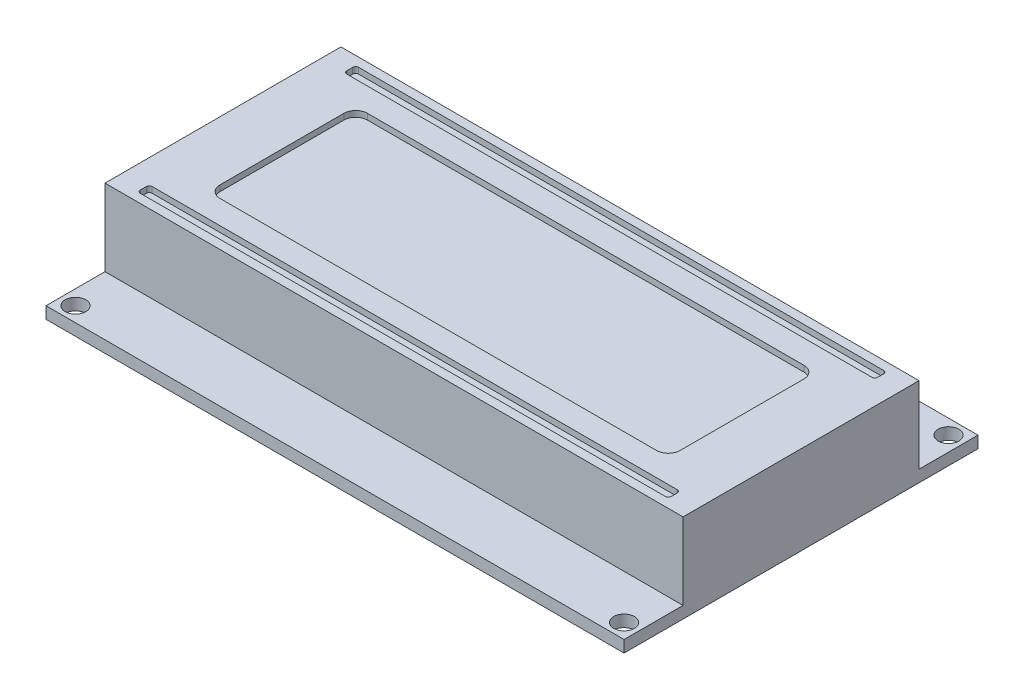
SolidWorks part; units mm, degrees
ref_plane "Front Plane" through (0, 0, 0) normal (0, 0, 1) x (1, 0, 0)
ref_plane "Top Plane" through (0, 0, 0) normal (0, 1, 0) x (1, 0, 0)
ref_plane "Right Plane" through (0, 0, 0) normal (1, 0, 0) x (0, 0, -1)
sketch "Sketch1" plane through (0, 0, 0) normal (0, 1, 0) x (1, 0, 0)
  line L0 (75, 55) -> (75, 0) construction
  line L1 (0, 0) -> (150, 0)
  line L2 (0, 0) -> (0, 55)
  line L3 (0, 55) -> (150, 55)
  line L4 (150, 0) -> (150, 55)
  line L5 (0, 27.5) -> (150, 27.5) construction
  circle A0 centre (3, 52) radius 1.5
  circle A1 centre (147, 52) radius 1.5
  circle A2 centre (147, 3) radius 1.5
  circle A3 centre (3, 3) radius 1.5
  dimension "D3" = 3
  dimension "D1" = 55
  dimension "D2" = 150
  dimension "D4" = 3
  dimension "D5" = 3
extrude "Boss-Extrude1" add sketch "Sketch1" along normal blind 2
sketch "Sketch2" plane through (0, 2, 0) normal (0, 1, 0) x (1, 0, 0)
  line L0 (0, 0) -> (150, 0) construction
  line L1 (0, 0) -> (0, 55) construction
  circle A0 centre (13, 10) radius 6
  dimension "D1" = 12
  dimension "D2" = 10
  dimension "D3" = 13
extrude "Boss-Extrude2" add sketch "Sketch2" along normal blind 10
sketch "Sketch3" plane through (0, 2, 0) normal (0, 1, 0) x (1, 0, 0)
  line L0 (0, 27.5) -> (150, 27.5) construction
  line L1 (7, 33.5) -> (19, 33.5)
  line L2 (7, 33.5) -> (7, 21.5)
  line L3 (7, 21.5) -> (19, 21.5)
  line L4 (19, 33.5) -> (19, 21.5)
  line L5 (13, 0) -> (13, 55) construction
  line L6 (0, 0) -> (150, 0) construction
  line L7 (0, 55) -> (150, 55) construction
  line L8 (7, 27.5) -> (19, 27.5) construction
  circle A1 centre (13, 10) radius 6 construction
  point P4 (7, 27.5)
  point P16 (13, 27.5)
  point P19 (13, 16)
  dimension "D1" = 12
  dimension "D2" = 12
extrude "Boss-Extrude3" add sketch "Sketch3" along normal blind 25
sketch "Sketch4" plane through (0, 2, 0) normal (0, 1, 0) x (1, 0, 0)
  line L0 (13, 45.5) -> (13, 40.5) construction
  line L1 (10.5, 45.5) -> (15.5, 45.5)
  line L2 (10.5, 45.5) -> (10.5, 40.5)
  line L3 (10.5, 40.5) -> (15.5, 40.5)
  line L4 (15.5, 45.5) -> (15.5, 40.5)
  line L5 (10.5, 43) -> (15.5, 43) construction
  line L7 (13, 0) -> (13, 55) construction
  line L8 (7, 33.5) -> (19, 33.5) construction
  line L9 (150, 0) -> (150, 55) construction
  line L10 (127, 8) -> (86, 8)
  line L11 (127, 8) -> (127, 5)
  line L12 (127, 5) -> (86, 5)
  line L13 (86, 8) -> (86, 5)
  line L14 (0, 0) -> (150, 0) construction
  point P8 (13, 43)
  dimension "D1" = 5
  dimension "D2" = 5
  dimension "D3" = 7
  dimension "D4" = 23
  dimension "D5" = 41
  dimension "D6" = 3
  dimension "D7" = 5
extrude "Boss-Extrude4" add sketch "Sketch4" along normal blind 5
sketch "Sketch5" plane through (0, 7, 0) normal (0, 1, 0) x (1, 0, 0)
  line L0 (86, 5) -> (127, 5) construction
  line L1 (86, 8) -> (127, 8)
  line L2 (86, 8) -> (86, 5)
  line L3 (86, 5) -> (127, 5)
  line L4 (127, 8) -> (127, 5)
  line L5 (86, 5) -> (127, 5) construction
  line L6 (10.5, 43) -> (15.5, 43) construction
  line L7 (10.5, 45.5) -> (10.5, 40.5) construction
  line L8 (15.5, 40.5) -> (15.5, 45.5) construction
  line L10 (10.5, 45.5) -> (15.5, 45.5)
  line L11 (10.5, 45.5) -> (10.5, 40.5)
  line L12 (10.5, 40.5) -> (15.5, 40.5)
  line L13 (15.5, 45.5) -> (15.5, 40.5)
  circle A0 centre (13, 43) radius 1.5
  point P15 (13, 43)
  dimension "D1" = 3
extrude "Cut-Extrude1" cut sketch "Sketch5" against normal blind 2
sketch "Sketch6" plane through (0, 27, 0) normal (0, 1, 0) x (1, 0, 0)
  line L0 (10.3706, 26.0556) -> (15.6294, 26.0556)
  line L1 (7, 33.5) -> (19, 33.5)
  line L2 (7, 33.5) -> (7, 21.5)
  line L3 (7, 21.5) -> (19, 21.5)
  line L4 (19, 33.5) -> (19, 21.5)
  arc A0 (15.6294, 26.0556) -> (10.3706, 26.0556) centre (13, 27.5) ccw
  dimension "D1" = 6
extrude "Cut-Extrude2" cut sketch "Sketch6" against normal blind 13
sketch "Sketch7" plane through (0, 14, 0) normal (0, 1, 0) x (1, 0, 0)
  line L1 (7, 33.5) -> (19, 33.5)
  line L2 (7, 33.5) -> (7, 21.5)
  line L3 (7, 21.5) -> (19, 21.5)
  line L4 (19, 33.5) -> (19, 21.5)
  circle A0 centre (13, 27.5) radius 3.5
  line M4 (7, 33.5) -> (7, 21.5)
  line M5 (7, 21.5) -> (19, 21.5)
  line M6 (19, 21.5) -> (19, 33.5)
  line M7 (19, 33.5) -> (7, 33.5)
  dimension "D1" = 7
extrude "Cut-Extrude3" cut sketch "Sketch7" against normal blind 7 contours A0 M7 M4 M5 M6 region at (13, 14, -33.3303)
sketch "Sketch8" plane through (0, 12, 0) normal (0, 1, 0) x (1, 0, 0)
  circle A0 centre (13, 10) radius 1.25
  point P0 (13, 10)
  dimension "D1" = 2.5
extrude "Cut-Extrude4" cut sketch "Sketch8" against normal blind 5
sketch "Sketch9" plane through (0, 0, 0) normal (0, -1, 0) x (1, 0, 0)
  line L0 (0, -55) -> (150, -55) construction
  line L1 (149, -20) -> (131, -20)
  line L2 (149, -20) -> (149, -47)
  line L3 (149, -47) -> (124, -47)
  line L4 (124, -22) -> (124, -47)
  line L5 (150, 0) -> (150, -55) construction
  line L6 (124, -22) -> (129, -22)
  line L7 (129, -22) -> (131, -20)
  dimension "D1" = 8
  dimension "D2" = 27
  dimension "D3" = 1
  dimension "D4" = 25
  dimension "D5" = 2
  dimension "D6" = 5
  dimension "D7" = 45
extrude "Boss-Extrude5" add sketch "Sketch9" along normal blind 3
sketch "Sketch10" plane through (149, 0, 0) normal (1, 0, 0) x (0, 0, -1)
  line L0 (20, -1.5) -> (47, -1.5) construction
  line L1 (20, -3) -> (20, 0) construction
  line L2 (47, -3) -> (47, 0) construction
  line L3 (33.5, -3) -> (33.5, 0) construction
  line L4 (47, -3) -> (20, -3) construction
  line L5 (0, 0) -> (55, 0) construction
  line L6 (33.5, -2.25) -> (33.5, -0.75) construction
  line L7 (21, -2.25) -> (46, -2.25)
  line L8 (21, -2.25) -> (21, -0.75)
  line L9 (21, -0.75) -> (46, -0.75)
  line L10 (46, -2.25) -> (46, -0.75)
  line L11 (21, -1.5) -> (46, -1.5) construction
  point P20 (33.5, -1.5)
  point P21 (33.5, -1.5)
  dimension "D1" = 1.5
  dimension "D2" = 25
extrude "Cut-Extrude5" cut sketch "Sketch10" against normal blind 18
sketch "Sketch11" plane through (0, 5, 0) normal (0, 1, 0) x (1, 0, 0)
  line L0 (0, 0) -> (150, 0) construction
  line L1 (136, 64) -> (38, 64)
  line L2 (136, 64) -> (136, 4)
  line L3 (136, 4) -> (38, 4)
  line L4 (38, 64) -> (38, 4)
  line L5 (150, 0) -> (150, 55) construction
  line L6 (87, 64) -> (87, 4) construction
  line L7 (38, 34) -> (136, 34) construction
  circle A0 centre (40.5, 61.5) radius 1.75
  circle A1 centre (133.5, 61.5) radius 1.75
  circle A2 centre (133.5, 6.5) radius 1.75
  circle A3 centre (40.5, 6.5) radius 1.75
  point P12 (87, 34)
  dimension "D5" = 3.5
  dimension "D1" = 98
  dimension "D2" = 60
  dimension "D3" = 4
  dimension "D4" = 14
  dimension "D6" = 2.5
  dimension "D7" = 2.5
extrude "Boss-Extrude6" add sketch "Sketch11" along normal blind 2
sketch "Sketch12" plane through (0, 7, 0) normal (0, 1, 0) x (1, 0, 0)
  line L0 (38, 34) -> (136, 34) construction
  line L1 (38, 54) -> (136, 54)
  line L2 (38, 54) -> (38, 14)
  line L3 (38, 14) -> (136, 14)
  line L4 (136, 54) -> (136, 14)
  dimension "D1" = 40
extrude "Boss-Extrude7" add sketch "Sketch12" along normal blind 13
sketch "Sketch13" plane through (0, 20, 0) normal (0, 1, 0) x (1, 0, 0)
  line L0 (87, 54) -> (87, 14) construction
  line L1 (136, 54) -> (38, 54) construction
  line L2 (38, 14) -> (136, 14) construction
  line L3 (38, 34) -> (136, 34) construction
  line L4 (38, 54) -> (38, 14) construction
  line L5 (136, 14) -> (136, 54) construction
  line L6 (87, 46.5) -> (87, 21.5) construction
  line L7 (50, 46.5) -> (124, 46.5)
  line L8 (48, 44.5) -> (48, 23.5)
  line L9 (50, 21.5) -> (124, 21.5)
  line L10 (126, 44.5) -> (126, 23.5)
  line L11 (87, 52.5) -> (87, 50.5) construction
  line L12 (42.5, 52.5) -> (131.5, 52.5)
  line L13 (42, 52) -> (42, 51)
  line L14 (42.5, 50.5) -> (131.5, 50.5)
  line L15 (132, 52) -> (132, 51)
  line L16 (136, 54) -> (38, 54) construction
  line L17 (42, 52.5) -> (42, 50.5)
  line L18 (132, 52.5) -> (132, 50.5)
  line L19 (87, 15.5) -> (87, 17.5) construction
  line L20 (132, 16) -> (132, 17)
  line L21 (42, 16) -> (42, 17)
  line L22 (132, 15.5) -> (132, 17.5)
  line L23 (42.5, 17.5) -> (131.5, 17.5)
  line L24 (42, 15.5) -> (42, 17.5)
  line L25 (42.5, 15.5) -> (131.5, 15.5)
  arc A0 (131.5, 50.5) -> (132, 51) centre (131.5, 51) ccw
  arc A1 (131.5, 52.5) -> (132, 52) centre (131.5, 52) cw
  arc A2 (42, 51) -> (42.5, 50.5) centre (42.5, 51) ccw
  arc A3 (42.5, 52.5) -> (42, 52) centre (42.5, 52) ccw
  arc A4 (131.5, 15.5) -> (132, 16) centre (131.5, 16) ccw
  arc A5 (131.5, 17.5) -> (132, 17) centre (131.5, 17) cw
  arc A6 (42.5, 15.5) -> (42, 16) centre (42.5, 16) cw
  arc A7 (42.5, 17.5) -> (42, 17) centre (42.5, 17) ccw
  arc A8 (124, 46.5) -> (126, 44.5) centre (124, 44.5) cw
  arc A9 (48, 23.5) -> (50, 21.5) centre (50, 23.5) ccw
  arc A10 (50, 46.5) -> (48, 44.5) centre (50, 44.5) ccw
  arc A11 (124, 21.5) -> (126, 23.5) centre (124, 23.5) ccw
  point P18 (87, 34)
  point P19 (87, 34)
  point P62 (48, 21.5)
  point P65 (48, 46.5)
  dimension "D6" = 0.5
  dimension "D7" = 0.5
  dimension "D8" = 2
  dimension "D1" = 25
  dimension "D2" = 10
  dimension "D3" = 4
  dimension "D4" = 1.5
  dimension "D5" = 2
extrude "Cut-Extrude6" cut sketch "Sketch13" against normal blind 1 contours L15 L12 L13 L14 | L10 L7 L8 L9 | L21 L25 L20 L23 region at (87, 20, -34) region at (87, 20, -51.5) region at (87, 20, -16.5)
sketch "Sketch14" plane through (131, 0, 0) normal (1, 0, 0) x (0, 0, -1)
  line L1 (21, -0.75) -> (46, -0.75)
  line L2 (21, -0.75) -> (21, -2.25)
  line L3 (21, -2.25) -> (46, -2.25)
  line L4 (46, -0.75) -> (46, -2.25)
extrude "Boss-Extrude8" add sketch "Sketch14" along normal offset from surface (29 mm away) 11 up to face at (149, -1.5, -33.5) offset beyond the face yes
sketch "Sketch15" plane through (0, 2, 0) normal (0, 1, 0) x (1, 0, 0)
  line L1 (38, 64) -> (-8.6907, 64)
  line L2 (38, 64) -> (38, 4)
  line L3 (38, -2.9807) -> (-8.6907, -2.9807)
  line L4 (-8.6907, 64) -> (-8.6907, -2.9807)
  line L5 (38, 4) -> (136, 4)
  line L7 (38, -2.9807) -> (158.5564, -2.9807)
  line L8 (158.5564, 4) -> (158.5564, -2.9807)
  line L9 (158.5564, 4) -> (165.161, 4)
  line L10 (136, 4) -> (136, 64)
  line L11 (136, 64) -> (165.161, 64)
  line L12 (165.161, 4) -> (165.161, 64)
extrude "Cut-Extrude7" cut sketch "Sketch15" against normal blind 10 and the other way blind 76
sketch "Sketch16" plane through (0, 0, -4) normal (0, 0, 1) x (1, 0, 0)
  line L1 (38, 5) -> (136, 5)
  line L2 (38, 5) -> (38, -3)
  line L3 (38, -3) -> (136, -3)
  line L4 (136, 5) -> (136, -3)
extrude "Cut-Extrude8" cut sketch "Sketch16" against normal blind 69
